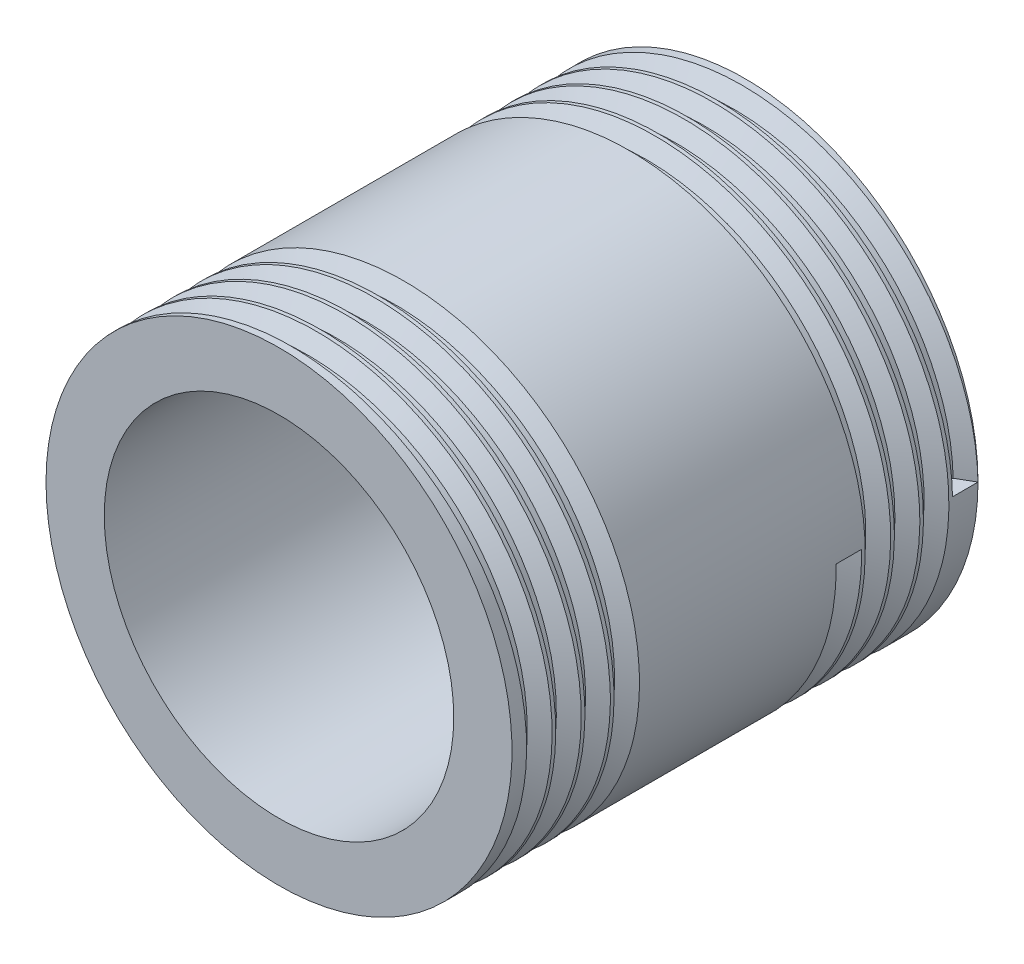
SolidWorks part; units mm, degrees
ref_plane "Front Plane" through (0, 0, 0) normal (0, 0, 1) x (1, 0, 0)
ref_plane "Top Plane" through (0, 0, 0) normal (0, 1, 0) x (1, 0, 0)
ref_plane "Right Plane" through (0, 0, 0) normal (1, 0, 0) x (0, 0, -1)
sketch "Sketch1" plane through (0, 0, 0) normal (0, 0, 1) x (1, 0, 0)
  circle A0 centre (0, 0) radius 19.05
  circle A1 centre (0, 0) radius 25.4
  dimension "D1" = 38.1
  dimension "D2" = 50.8
extrude "Boss-Extrude1" add sketch "Sketch1" along normal blind 50.8
thread "Thread1" pitch 3.175 method cut profile "Thread Profile1" start angle 0, offset 0, length 12.7, pitch 3.175, diameter 50.8
ref_plane "Plane1" through (-25.4, 0, 50.8) normal (0, -1, 0) x (-1, 0, 0)
sketch "Thread Profile1" plane through (-25.4, 0, 50.8) normal (0, -1, 0) x (-1, 0, 0)
  line L0 (0, 0) -> (0, 3.175) construction
  line L11 (0, 0) -> (0, 2.7781)
  line L12 (0, 2.7781) -> (-1.7185, 1.7859)
  line L13 (-1.7185, 1.7859) -> (-1.7185, 0.9922)
  line L15 (-1.7185, 0.9922) -> (0, 0)
  line L17 (-1.7185, 1.3891) -> (0, 1.3891) construction
  point P2 (0, 0)
  dimension "Pitch" = 3.175
  dimension "Profile_Angle" = 60
  dimension "Profile_Land" = 0.7937
  dimension "Profile_Height" = 1.7185
thread "Thread2" pitch 3.175 method cut profile "Thread Profile2" start angle 0, offset 0, length 12.7, pitch 3.175, diameter 50.8
ref_plane "Plane2" through (25.4, 0, 0) normal (0, -1, 0) x (1, 0, 0)
sketch "Thread Profile2" plane through (25.4, 0, 0) normal (0, -1, 0) x (1, 0, 0)
  line L0 (0, 0) -> (0, 3.175) construction
  line L11 (0, 0) -> (0, 2.7781)
  line L12 (0, 2.7781) -> (-1.7185, 1.7859)
  line L13 (-1.7185, 1.7859) -> (-1.7185, 0.9922)
  line L15 (-1.7185, 0.9922) -> (0, 0)
  line L17 (-1.7185, 1.3891) -> (0, 1.3891) construction
  point P2 (0, 0)
  dimension "Pitch" = 3.175
  dimension "Profile_Angle" = 60
  dimension "Profile_Land" = 0.7937
  dimension "Profile_Height" = 1.7185
